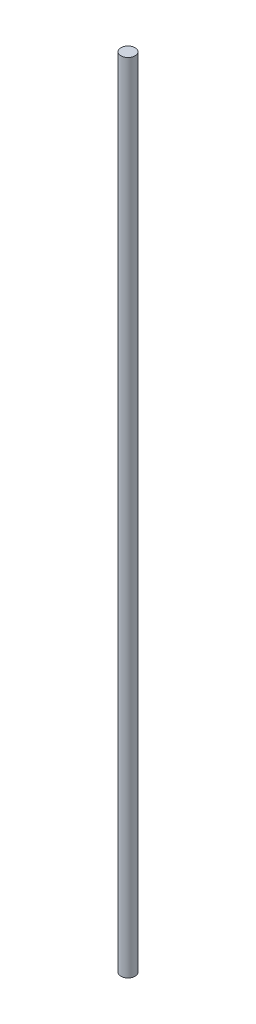
SolidWorks part; units mm, degrees
material "AISI Type A2 Tool Steel"
ref_plane "Front Plane" through (0, 0, 0) normal (0, 0, 1) x (1, 0, 0)
ref_plane "Top Plane" through (0, 0, 0) normal (0, 1, 0) x (1, 0, 0)
ref_plane "Right Plane" through (0, 0, 0) normal (1, 0, 0) x (0, 0, -1)
sketch "Sketch1" plane through (0, 0, 0) normal (0, 1, 0) x (1, 0, 0)
  circle A0 centre (0, 0) radius 1.5
  dimension "D1" = 3
extrude "Boss-Extrude1" add sketch "Sketch1" along normal blind 170
